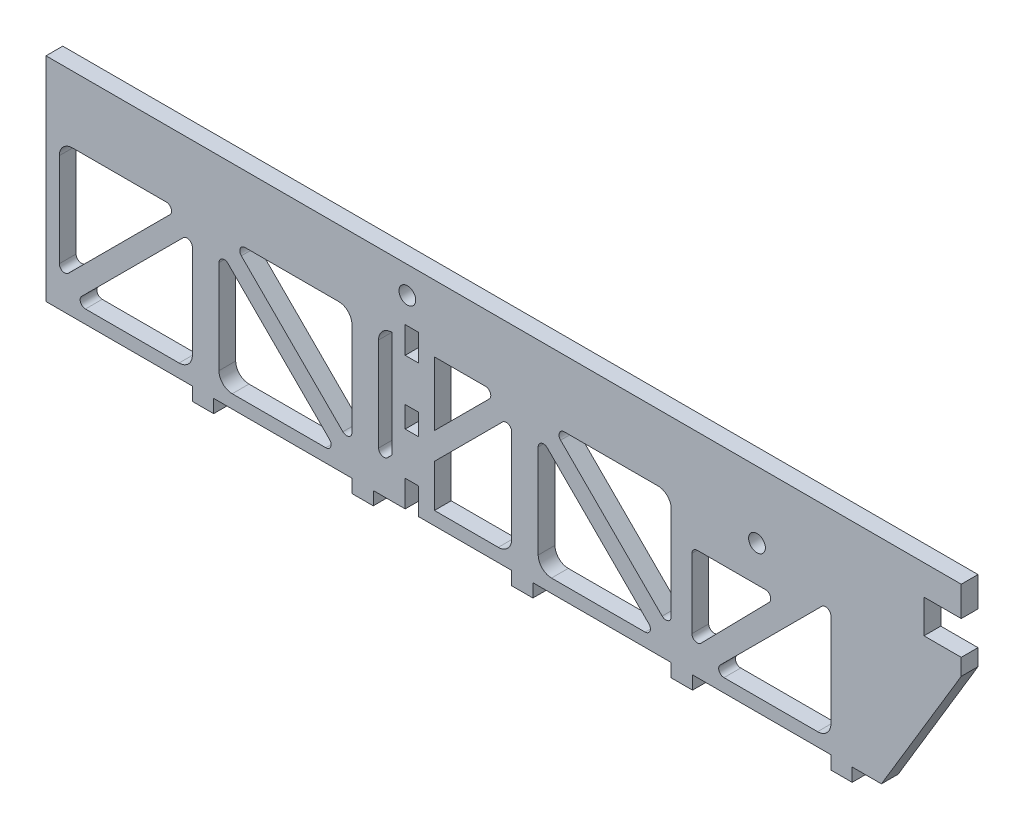
SolidWorks part; units mm, degrees
material "Pine"
ref_plane "Front Plane" through (0, 0, 0) normal (0, 0, 1) x (1, 0, 0)
ref_plane "Top Plane" through (0, 0, 0) normal (0, 1, 0) x (1, 0, 0)
ref_plane "Right Plane" through (0, 0, 0) normal (1, 0, 0) x (0, 0, -1)
sketch "Model" plane through (0, 0, 0) normal (0, 0, 1) x (1, 0, 0)
  line L0 (312.6855, 15.1239) -> (345.2281, 48.2988)
  line L1 (343.4149, 52.6175) -> (310.8722, 52.6175)
  line L2 (308.3322, 50.0775) -> (308.3322, 16.9026)
  line L8 (171.2321, 6.35) -> (215.9, 6.35)
  line L9 (217.9139, 59.1639) -> (169.4361, 10.6861)
  line L10 (222.25, 57.3679) -> (222.25, 12.7)
  line L11 (234.95, 57.3679) -> (234.95, 12.7)
  line L12 (239.2861, 59.1639) -> (287.7639, 10.6861)
  line L13 (241.3, 6.35) -> (285.9679, 6.35)
  line L14 (294.1139, 17.0361) -> (245.6361, 65.5139)
  line L15 (247.4321, 69.85) -> (292.1, 69.85)
  line L16 (298.45, 63.5) -> (298.45, 18.8321)
  line L17 (323.6321, 6.35) -> (368.3, 6.35)
  line L18 (370.3139, 59.1639) -> (321.8361, 10.6861)
  line L19 (374.65, 57.3679) -> (374.65, 12.7)
  line L20 (18.8321, 6.35) -> (63.5, 6.35)
  line L21 (17.0361, 10.6861) -> (65.5139, 59.1639)
  line L22 (69.85, 57.3679) -> (69.85, 12.7)
  line L23 (82.55, 57.3679) -> (82.55, 12.7)
  line L24 (86.8861, 59.1639) -> (135.3639, 10.6861)
  line L25 (88.9, 6.35) -> (133.5679, 6.35)
  line L26 (93.2361, 65.5139) -> (141.7139, 17.0361)
  line L27 (95.0321, 69.85) -> (139.7, 69.85)
  line L28 (146.05, 63.5) -> (146.05, 18.8321)
  line L29 (163.0861, 17.0361) -> (211.5639, 65.5139)
  line L30 (158.75, 63.5) -> (158.75, 18.8321)
  line L31 (165.1, 69.85) -> (209.7679, 69.85)
  line L35 (419.1, 87.376) -> (419.1, 71.374)
  line L36 (436.88, 87.376) -> (419.1, 87.376)
  line L37 (436.88, 87.376) -> (436.88, 95.25)
  line L38 (0, 95.25) -> (436.88, 95.25)
  line L39 (0, 0) -> (0, 95.25)
  line L40 (0, 0) -> (398.78, 0)
  line L41 (436.88, 63.5) -> (398.78, 0)
  line L42 (436.88, 63.5) -> (436.88, 71.374)
  line L43 (419.1, 71.374) -> (436.88, 71.374)
  line L44 (6.35, 63.5) -> (6.35, 18.8321)
  line L45 (12.7, 69.85) -> (57.3679, 69.85)
  line L46 (59.1639, 65.5139) -> (10.6861, 17.0361)
  arc A0 (215.9, 6.35) -> (222.25, 12.7) centre (215.9, 12.7) ccw
  arc A1 (169.4361, 10.6861) -> (171.2321, 6.35) centre (171.2321, 8.89) ccw
  arc A2 (222.25, 57.3679) -> (217.9139, 59.1639) centre (219.71, 57.3679) ccw
  arc A3 (239.2861, 59.1639) -> (234.95, 57.3679) centre (237.49, 57.3679) ccw
  arc A4 (285.9679, 6.35) -> (287.7639, 10.6861) centre (285.9679, 8.89) ccw
  arc A5 (234.95, 12.7) -> (241.3, 6.35) centre (241.3, 12.7) ccw
  arc A6 (247.4321, 69.85) -> (245.6361, 65.5139) centre (247.4321, 67.31) ccw
  arc A7 (298.45, 63.5) -> (292.1, 69.85) centre (292.1, 63.5) ccw
  arc A8 (294.1139, 17.0361) -> (298.45, 18.8321) centre (295.91, 18.8321) ccw
  arc A9 (321.8361, 10.6861) -> (323.6321, 6.35) centre (323.6321, 8.89) ccw
  arc A10 (374.65, 57.3679) -> (370.3139, 59.1639) centre (372.11, 57.3679) ccw
  arc A11 (368.3, 6.35) -> (374.65, 12.7) centre (368.3, 12.7) ccw
  arc A12 (63.5, 6.35) -> (69.85, 12.7) centre (63.5, 12.7) ccw
  arc A13 (17.0361, 10.6861) -> (18.8321, 6.35) centre (18.8321, 8.89) ccw
  arc A14 (69.85, 57.3679) -> (65.5139, 59.1639) centre (67.31, 57.3679) ccw
  arc A15 (86.8861, 59.1639) -> (82.55, 57.3679) centre (85.09, 57.3679) ccw
  arc A16 (133.5679, 6.35) -> (135.3639, 10.6861) centre (133.5679, 8.89) ccw
  arc A17 (82.55, 12.7) -> (88.9, 6.35) centre (88.9, 12.7) ccw
  arc A18 (95.0321, 69.85) -> (93.2361, 65.5139) centre (95.0321, 67.31) ccw
  arc A19 (146.05, 63.5) -> (139.7, 69.85) centre (139.7, 63.5) ccw
  arc A20 (141.7139, 17.0361) -> (146.05, 18.8321) centre (143.51, 18.8321) ccw
  arc A21 (158.75, 18.8321) -> (163.0861, 17.0361) centre (161.29, 18.8321) ccw
  arc A22 (165.1, 69.85) -> (158.75, 63.5) centre (165.1, 63.5) ccw
  arc A23 (211.5639, 65.5139) -> (209.7679, 69.85) centre (209.7679, 67.31) ccw
  arc A24 (345.2281, 48.2988) -> (343.4149, 52.6175) centre (343.4149, 50.0775) ccw
  arc A25 (310.8722, 52.6175) -> (308.3322, 50.0775) centre (310.8722, 50.0775) ccw
  arc A26 (312.6855, 15.1239) -> (308.3322, 16.9026) centre (310.8722, 16.9026) cw
  arc A27 (6.35, 18.8321) -> (10.6861, 17.0361) centre (8.89, 18.8321) ccw
  arc A28 (12.7, 69.85) -> (6.35, 63.5) centre (12.7, 63.5) ccw
  arc A29 (59.1639, 65.5139) -> (57.3679, 69.85) centre (57.3679, 67.31) ccw
  circle A30 centre (172.4917, 88.8013) radius 4
  circle A32 centre (172.4917, 88.8013) radius 167.9707 construction
  circle A33 centre (339.3899, 69.85) radius 4
  dimension "D2" = 6.4487
  dimension "D3" = 172.4917
  dimension "D4" = 8
  dimension "D8" = 2.54
  dimension "D1" = 95.25
extrude "Boss-Extrude2" add sketch "Model" along normal blind 8
sketch "Sketch1" plane through (0, 0, 8) normal (0, 0, 1) x (1, 0, 0)
  line L0 (69.85, 12.7) -> (69.85, 0) construction
  line L1 (146.05, 95.25) -> (146.05, 0) construction
  line L2 (146.05, 18.8321) -> (146.05, 63.5) construction
  line L3 (0, 0) -> (398.78, 0) construction
  line L4 (222.25, 95.25) -> (222.25, 0) construction
  line L5 (222.25, 12.7) -> (222.25, 57.3679) construction
  line L6 (298.45, 18.8321) -> (298.45, 0) construction
  line L7 (146.05, 0) -> (156.21, 0)
  line L8 (69.85, 0) -> (80.01, 0)
  line L9 (69.85, 0) -> (69.85, -6.35)
  line L10 (69.85, -6.35) -> (80.01, -6.35)
  line L11 (80.01, 0) -> (80.01, -6.35)
  line L16 (222.25, 0) -> (232.41, 0)
  line L17 (222.25, 0) -> (222.25, -6.35)
  line L18 (222.25, -6.35) -> (232.41, -6.35)
  line L19 (232.41, 0) -> (232.41, -6.35)
  line L20 (146.05, 0) -> (146.05, -6.35)
  line L21 (146.05, -6.35) -> (156.21, -6.35)
  line L22 (156.21, 0) -> (156.21, -6.35)
  line L24 (374.65, 12.7) -> (374.65, 0) construction
  line L25 (374.65, 12.7) -> (374.65, 57.3679) construction
  line L27 (298.45, 0) -> (308.61, 0)
  line L28 (298.45, 0) -> (298.45, -6.35)
  line L29 (298.45, -6.35) -> (308.61, -6.35)
  line L30 (308.61, 0) -> (308.61, -6.35)
  line L31 (374.65, 0) -> (384.81, 0)
  line L32 (374.65, 0) -> (374.65, -6.35)
  line L33 (374.65, -6.35) -> (384.81, -6.35)
  line L34 (384.81, 0) -> (384.81, -6.35)
  line L39 (0, 101.6) -> (436.88, 101.6)
  line L53 (0, 95.25) -> (0, 101.6)
  line L55 (436.88, 95.25) -> (436.88, 101.6)
  line L56 (436.88, 95.25) -> (0, 95.25) construction
  line L57 (0, 95.25) -> (436.88, 95.25)
  arc A0 (368.3, 6.35) -> (374.65, 12.7) centre (368.3, 12.7) ccw construction
  dimension "D1" = 10.16
  dimension "D2" = 6.35
  dimension "D3" = 10.16
  dimension "D4" = 6.35
  dimension "D5" = 10.16
  dimension "D6" = 10.16
  dimension "D7" = 10.16
  dimension "D13" = 6.35
extrude "Boss-Extrude3" add sketch "Sketch1" against normal up to surface (8 mm away) up to face at (321.5295, 39.2174, 0)
sketch "Sketch2" plane through (0, 0, 8) normal (0, 0, 1) x (1, 0, 0)
  line L0 (156.21, 0) -> (222.25, 0) construction
  line L1 (165.1, 79.7539) -> (185.42, 79.7539)
  line L2 (165.1, 79.7539) -> (165.1, 0)
  line L3 (165.1, 0) -> (185.42, 0)
  line L4 (185.42, 79.7539) -> (185.42, 0)
  line L5 (158.75, 63.5) -> (158.75, 18.8321) construction
  line L7 (171.45, 0) -> (177.8, 0)
  line L8 (171.45, 0) -> (171.45, 12.7)
  line L9 (171.45, 12.7) -> (177.8, 12.7)
  line L10 (177.8, 0) -> (177.8, 12.7)
  line L11 (171.45, 33.02) -> (177.8, 33.02)
  line L12 (171.45, 33.02) -> (171.45, 43.18)
  line L13 (171.45, 43.18) -> (177.8, 43.18)
  line L14 (177.8, 33.02) -> (177.8, 43.18)
  line L15 (171.45, 63.5) -> (177.8, 63.5)
  line L16 (171.45, 63.5) -> (171.45, 76.2)
  line L17 (171.45, 76.2) -> (177.8, 76.2)
  line L18 (177.8, 63.5) -> (177.8, 76.2)
  line L19 (146.05, -6.35) -> (156.21, -6.35) construction
  dimension "D1" = 6.35
  dimension "D2" = 20.32
  dimension "D3" = 6.35
  dimension "D4" = 6.35
  dimension "D5" = 6.35
  dimension "D6" = 12.7
  dimension "D7" = 20.32
  dimension "D8" = 20.32
  dimension "D9" = 10.16
  dimension "D10" = 12.7
extrude "Boss-Extrude4" add sketch "Sketch2" against normal up to surface (8 mm away) contours L10 L3 L4 L1 L2 L8 L9 L18 L15 L16 L17 L14 L11 L12 L13 region at (175.26, 78.9309, 8) up to face at (321.5295, 39.2174, 0)
extrude "Cut-Extrude1" cut sketch "Sketch2<3>" along direction (0, 0, 1) on the side against the normal up to surface (8 mm away) from surface contours L3 L10 L9 L8 | L15 L18 L17 L16 region at (174.625, 6.35, 8) region at (174.625, 69.85, 8) up to face at (174.625, 9.525, 0) starting at face at (174.625, 9.525, 8)
sketch "Sketch2<3>" plane through (0, 0, 8) normal (0, 0, 1) x (1, 0, 0) same geometry as "Sketch2"
